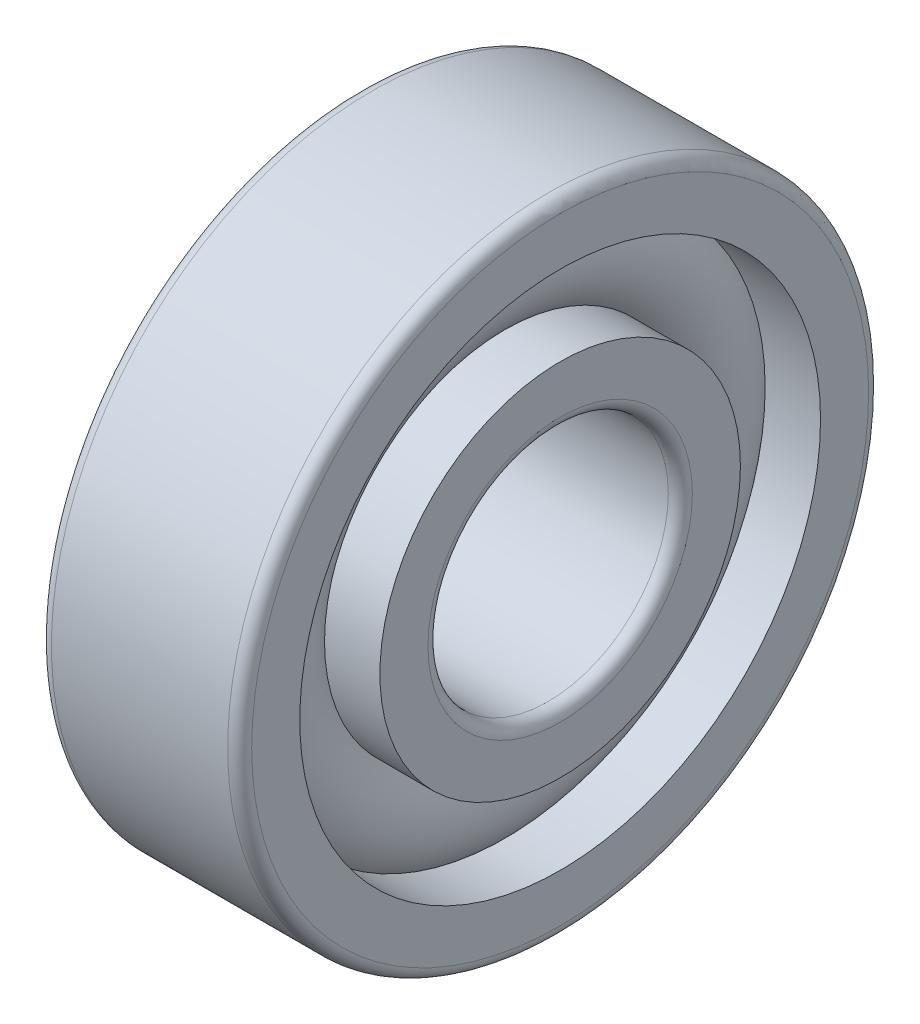
SolidWorks part; units mm, degrees
ref_plane "Plane1" through (0, 0, 0) normal (0, 0, 1) x (1, 0, 0)
ref_plane "Plane2" through (0, 0, 0) normal (0, 1, 0) x (1, 0, 0)
ref_plane "Plane3" through (0, 0, 0) normal (1, 0, 0) x (0, 0, -1)
sketch "Clipboard" plane through (0, 0, 0) normal (0, 0, 1) x (1, 0, 0)
  line L0 (-10, 0) -> (10, 0) construction
  line L1 (0, 0) -> (22.3471, -0.7804)
  line L2 (0, 0) -> (10.9933, 0.3839)
  line L3 (0, 0) -> (22.3471, -0.7804)
  line L4 (0, 0) -> (-22.3573, -0.3902)
  dimension "BallCLRad" = 11
sketch "CagSpiSke" plane through (0, 0, 0) normal (0, 0, 1) x (1, 0, 0)
  line L0 (0.3, 10.5) -> (0.3, 11.5)
  line L1 (0.3, 11.5) -> (-0.3, 11.5)
  line L2 (-0.3, 11.5) -> (-0.3, 10.5)
  line L3 (-0.3, 10.5) -> (0.3, 10.5)
  line L4 (-20.6375, 0) -> (20.6375, 0) construction
  line L5 (0, 0) -> (0, 23.7692) construction
  dimension "OD" = 23
  dimension "ID" = 21
revolve "CageSpine" add sketch "CagSpiSke" angle 0.001 about L4 reverse direction yes
ref_axis "Axis1" through (-50, 0, 0) along (1, 0, 0)
sketch "CagBalSke" plane through (0, 0, 0) normal (0, 0, 1) x (1, 0, 0)
  line L0 (-3.3, 11) -> (3.3, 11)
  line L1 (-1.905, 11) -> (1.905, 11) construction
  line L2 (-10, 0) -> (10, 0) construction
  line L3 (0, 0) -> (0, 24) construction
  arc A0 (3.3, 11) -> (-3.3, 11) centre (0, 11) cw
  dimension "BallCLRad" = 11
revolve "CageBall" [suppressed] add sketch "CagBalSke" angle 360 about L1 reverse direction yes
pattern_circular "CageBalls" [suppressed] count 2 every 180 about axis through (-50, 0, 0) along (1, 0, 0)
sketch "CagTrmODSke" plane through (0, 0, 0) normal (0, 0, 1) x (1, 0, 0)
  line L0 (3.301, 11.5) -> (3.301, 14.301)
  line L1 (3.301, 14.301) -> (-3.301, 14.301)
  line L2 (-3.301, 14.301) -> (-3.301, 11.5)
  line L3 (-3.301, 11.5) -> (3.301, 11.5)
  line L4 (-20.6375, 0) -> (20.6375, 0) construction
  line L5 (0, 0) -> (0, 25) construction
  dimension "Width" = 6.602
  dimension "ID" = 23
  dimension "OD" = 28.602
revolve "CageTrimOD" [suppressed] cut sketch "CagTrmODSke" angle 360 about L4 reverse direction yes
sketch "CagTrmIDSke" plane through (0, 0, 0) normal (0, 0, 1) x (1, 0, 0)
  line L0 (3.301, 7.701) -> (3.301, 10.5)
  line L1 (3.301, 10.5) -> (-3.301, 10.5)
  line L2 (-3.301, 10.5) -> (-3.301, 7.701)
  line L3 (-3.301, 7.701) -> (3.301, 7.701)
  line L4 (-20.6375, 0) -> (20.6375, 0) construction
  line L5 (0, 0) -> (0, 25) construction
  dimension "Width" = 6.602
  dimension "ID" = 15.402
  dimension "OD" = 21
revolve "CageTrimID" [suppressed] cut sketch "CagTrmIDSke" angle 360 about L4 reverse direction yes
sketch "BalSimSke" plane through (0, 0, 0) normal (0, 0, 1) x (1, 0, 0)
  line L0 (-10, 0) -> (10, 0) construction
  line L1 (-10, 11) -> (10, 11) construction
  line L2 (0, 0) -> (0, 23) construction
  circle A0 centre (0, 11) radius 3
  dimension "BallCLRad" = 11
  dimension "Ball_diameter" = 6
revolve "BallsSimplified" add sketch "BalSimSke" angle 360 about L0
sketch "BalDetSke" plane through (0, 0, 0) normal (0, 0, 1) x (1, 0, 0)
  line L0 (-3, 11) -> (3, 11)
  line L1 (-1.905, 11) -> (1.905, 11) construction
  line L2 (0, 0) -> (0, 25) construction
  arc A0 (3, 11) -> (-3, 11) centre (0, 11) cw
  dimension "BallCLRad" = 11
  dimension "Ball_diameter" = 6
revolve "BallDetailed" [suppressed] add sketch "BalDetSke" angle 360 about L1 reverse direction yes
sketch "InnRacSke" plane through (0, 0, 0) normal (0, 0, 1) x (1, 0, 0)
  line L0 (-2.2024, 9) -> (-5, 9)
  line L1 (-5, 9) -> (-5, 6.6)
  line L2 (-4.4, 6) -> (4.4, 6)
  line L3 (5, 6.6) -> (5, 9)
  line L4 (5, 9) -> (2.2024, 9)
  line L5 (-20.6375, 0) -> (20.6375, 0) construction
  line L6 (0, 0) -> (0, 30) construction
  arc A0 (-5, 6.6) -> (-4.4, 6) centre (-4.4, 6.6) ccw
  arc A1 (4.4, 6) -> (5, 6.6) centre (4.4, 6.6) ccw
  arc A2 (2.2024, 9) -> (-2.2024, 9) centre (0, 11) cw
  dimension "BallCLRad" = 11
  dimension "Fillet_radius" = 0.6
  dimension "Ball_diameter" = 5.95
  dimension "ID" = 12
  dimension "OD" = 18
  dimension "Width" = 10
revolve "InnerRace" add sketch "InnRacSke" angle 360 about L5 reverse direction yes
sketch "OutRacSke" plane through (0, 0, 0) normal (0, 0, 1) x (1, 0, 0)
  line L0 (-2.2024, 13) -> (-5, 13)
  line L1 (-5, 13) -> (-5, 15.4)
  line L2 (-4.4, 16) -> (4.4, 16)
  line L3 (5, 15.4) -> (5, 13)
  line L4 (5, 13) -> (2.2024, 13)
  line L5 (-20.6375, 0) -> (20.6375, 0) construction
  line L6 (0, 0) -> (0, 30) construction
  arc A0 (-5, 15.4) -> (-4.4, 16) centre (-4.4, 15.4) cw
  arc A1 (4.4, 16) -> (5, 15.4) centre (4.4, 15.4) cw
  arc A2 (2.2024, 13) -> (-2.2024, 13) centre (0, 11) ccw
  dimension "BallCLRad" = 11
  dimension "Fillet_radius" = 0.6
  dimension "Ball_diameter" = 5.95
  dimension "Width" = 10
revolve "OuterRace" add sketch "OutRacSke" angle 360 about L5 reverse direction yes
pattern_circular "BallsDetailed" [suppressed] count 2 every 180 about axis through (-50, 0, 0) along (1, 0, 0)
equation "\"BallCLRad@Clipboard\" = ( \"OD@OutRacSke\" + \"ID@InnRacSke\" ) / 4"
equation "\"BallCLRad@BalSimSke\" = \"BallCLRad@Clipboard\""
equation "\"BallCLRad@BalDetSke\" = \"BallCLRad@Clipboard\""
equation "\"BallCLRad@InnRacSke\" = \"BallCLRad@Clipboard\""
equation "\"BallCLRad@OutRacSke\" = \"BallCLRad@Clipboard\""
equation "\"Ball_diameter@InnRacSke\" = \"Ball_diameter@BalDetSke\" - 0.05"
equation "\"Ball_diameter@OutRacSke\" = \"Ball_diameter@BalDetSke\" - 0.05"
equation "\"Ball_diameter@BalSimSke\" = \"Ball_diameter@BalDetSke\""
equation "\"Width@OutRacSke\" = \"Width@InnRacSke\""
equation "\"Fillet_radius@OutRacSke\" = \"Fillet_radius@InnRacSke\""
equation "\"Max_count@Clipboard\" = int( 3.14159265 / atn(( \"Ball_diameter@BalDetSke\" / 2) / sqr( \"BallCLRad@Clipboard\"  *  \"BallCLRad@Clipboard\" - ( \"Ball_diameter@BalDetSke\" / 2) *  ( \"Ball_diameter@BalDetSke\" / 2))))"
equation "\"Max_count@Clipboard\" = ((sgn( \"Max_count@Clipboard\" - \"Count@Clipboard\" )-1)*( \"Max_count@Clipboard\" - \"Count@Clipboard\" ))/-2+ \"Count@Clipboard\""
equation "\"Count@BallsDetailed\" = int( \"Show_count@Clipboard\" ) "
equation "\"Count@BallsDetailed\" = ((sgn( \"Count@BallsDetailed\" - \"Max_count@Clipboard\" )-1)*( \"Count@BallsDetailed\" - \"Max_count@Clipboard\" ))/-2+ \"Max_count@Clipboard\""
equation "\"Count@BallsDetailed\" = ((sgn( \"Count@BallsDetailed\" - \"Min_count@Clipboard\" )+1)*( \"Count@BallsDetailed\" - \"Min_count@Clipboard\"))/2 +\"Min_count@Clipboard\""
equation "\"Angle@BallsDetailed\" = 360.0 / \"Max_count@Clipboard\""
equation "\"BallCLRad@CagBalSke\" = \"BallCLRad@Clipboard\""
equation "\"Count@CageBalls\" = \"Count@BallsDetailed\""
equation "\"Angle@CageBalls\" = \"Angle@BallsDetailed\""
equation "\"Angle@CageSpine\" =  \"Angle@CageBalls\" * ( \"Count@CageBalls\" -1 + int( \"Count@CageBalls\" / \"Max_count@Clipboard\" ) )  + 0.001 -  int( \"Count@CageBalls\" / \"Max_count@Clipboard\" ) * 0.001"
equation "\"Angle@CageSpine\" =  \"Angle@CageSpine\" * int( \"Min_count@Clipboard\" / 2) + int(1 / \"Min_count@Clipboard\")  * 0.001"
equation "\"CageWallOD@CagBalSke\" =  \"Ball_diameter@BalDetSke\" * 1.1"
equation "\"Thickness@CagSpiSke\" =  \"Ball_diameter@BalDetSke\" * 0.1"
equation "\"OD@CagTrmODSke\" = \"BallCLRad@Clipboard\" * 2 + \"CageWallOD@CagBalSke\" + 0.002"
equation "\"ID@CagTrmODSke\" = \"BallCLRad@Clipboard\" * 2 + \"Ball_diameter@BalDetSke\" / 6"
equation "\"OD@CagTrmIDSke\" = \"BallCLRad@Clipboard\" * 2 - \"Ball_diameter@BalDetSke\" / 6"
equation "\"ID@CagTrmIDSke\" = \"BallCLRad@Clipboard\" * 2 - \"CageWallOD@CagBalSke\" + 0.002"
equation "\"OD@CagSpiSke\" = \"ID@CagTrmODSke\""
equation "\"ID@CagSpiSke\" = \"OD@CagTrmIDSke\""
equation "\"Width@CagTrmODSke\" = \"CageWallOD@CagBalSke\" + 0.002"
equation "\"Width@CagTrmIDSke\" = \"CageWallOD@CagBalSke\" + 0.002"
